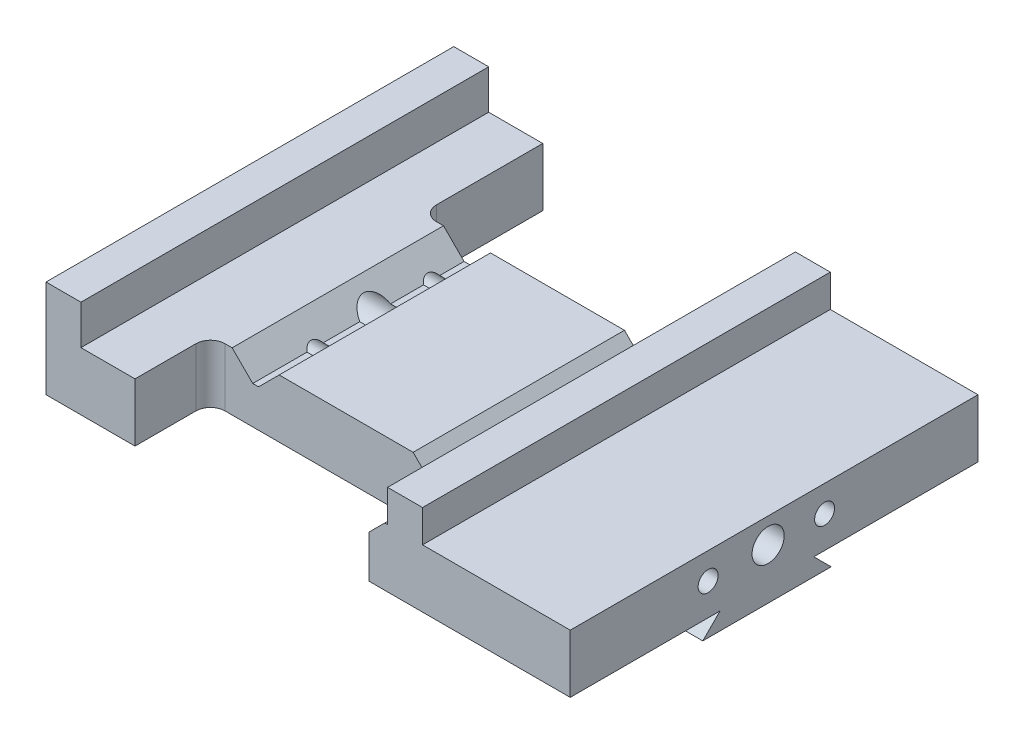
SolidWorks part; units mm, degrees
ref_plane "Front Plane" through (0, 0, 0) normal (0, 0, 1) x (1, 0, 0)
ref_plane "Top Plane" through (0, 0, 0) normal (0, 1, 0) x (1, 0, 0)
ref_plane "Right Plane" through (0, 0, 0) normal (1, 0, 0) x (0, 0, -1)
sketch "Sketch1" plane through (0, 0, 0) normal (0, 0, 1) x (1, 0, 0)
  line L0 (-151.9042, 0.4789) -> (-151.9042, 20.5906)
  line L1 (-151.9042, 20.5906) -> (-139.9042, 20.5906)
  line L2 (-139.9042, 20.5906) -> (-139.9042, 7.0711)
  line L3 (-139.9042, 7.0711) -> (-113.9042, 7.0711)
  line L4 (-113.9042, 7.0711) -> (-106.8331, 0)
  line L5 (-106.8331, 0) -> (-104.8331, 0)
  line L6 (-104.8331, 0) -> (-97.762, 7.0711)
  line L7 (-97.762, 7.0711) -> (-51.762, 7.0711)
  line L8 (-51.762, 7.0711) -> (-44.691, 0)
  line L9 (-44.691, 0) -> (-42.691, 0)
  line L10 (-42.691, 0) -> (-35.6199, 7.0711)
  line L11 (-35.6199, 7.0711) -> (-34.6199, 7.0711)
  line L12 (-34.6199, 7.0711) -> (-34.6199, 18.18)
  line L13 (-34.6199, 18.18) -> (-22.6199, 18.18)
  line L14 (-22.6199, 18.18) -> (-22.6199, 7.0711)
  line L15 (-22.6199, 7.0711) -> (28.0958, 7.0711)
  line L16 (28.0958, 7.0711) -> (28.0958, -12.9289)
  line L17 (28.0958, -12.9289) -> (-151.9042, -12.9289)
  line L18 (-151.9042, -12.9289) -> (-151.9042, 0.4789)
  dimension "D1" = 180
  dimension "D2" = 10
  dimension "D3" = 10
  dimension "D4" = 2
  dimension "D5" = 10
  dimension "D6" = 10
  dimension "D7" = 2
  dimension "D8" = 12
  dimension "D9" = 46
  dimension "D10" = 1
  dimension "D11" = 12
  dimension "D12" = 225
  dimension "D13" = 20
  dimension "D14" = 26
extrude "Boss-Extrude1" add sketch "Sketch1" along normal blind 140
sketch "Sketch2" plane through (28.0958, 0, 0) normal (1, 0, 0) x (0, 0, -1)
  line L0 (-88.5445, -12.9289) -> (-94.4984, -18.8828)
  line L1 (-140, -12.9289) -> (0, -12.9289) construction
  line L2 (-94.4984, -18.8828) -> (-50.4097, -18.8828)
  line L3 (-50.4097, -18.8828) -> (-56.3636, -12.9289)
  line L4 (-56.3636, -12.9289) -> (-88.5445, -12.9289)
  dimension "D1" = 45
  dimension "D2" = 45
extrude "Boss-Extrude2" add sketch "Sketch2" against normal blind 180
sketch "Sketch3" plane through (0, -12.9289, 0) normal (0, -1, 0) x (1, 0, 0)
  line L0 (-151.9042, 0) -> (28.0958, 0) construction
  line L1 (-121.3429, 0) -> (-41.0392, 0)
  line L2 (-121.3429, 0) -> (-121.3429, 36.5202)
  line L3 (-116.3429, 41.5202) -> (-46.0392, 41.5202)
  line L4 (-41.0392, 0) -> (-41.0392, 36.5202)
  line L5 (-151.9042, 140) -> (28.0958, 140) construction
  line L6 (-121.3429, 140) -> (-41.0392, 140)
  line L7 (-121.3429, 140) -> (-121.3429, 119.087)
  line L8 (-116.3429, 114.087) -> (-46.0392, 114.087)
  line L9 (-41.0392, 140) -> (-41.0392, 119.087)
  arc A0 (-46.0392, 41.5202) -> (-41.0392, 36.5202) centre (-46.0392, 36.5202) cw
  arc A1 (-121.3429, 36.5202) -> (-116.3429, 41.5202) centre (-116.3429, 36.5202) cw
  arc A2 (-46.0392, 114.087) -> (-41.0392, 119.087) centre (-46.0392, 119.087) ccw
  arc A3 (-121.3429, 119.087) -> (-116.3429, 114.087) centre (-116.3429, 119.087) ccw
  dimension "D1" = 5
extrude "Cut-Extrude1" cut sketch "Sketch3" against normal blind 100
sketch "Sketch4" plane through (28.0958, 0, 0) normal (1, 0, 0) x (0, 0, -1)
  circle A0 centre (-72.0525, -1.5555) radius 5.5191
extrude "Cut-Extrude2" cut sketch "Sketch4" against normal blind 1000
sketch "Sketch5" plane through (28.0958, 0, 0) normal (1, 0, 0) x (0, 0, -1)
  circle A0 centre (-92.6666, -2.0017) radius 3.4284
  circle A2 centre (-52.6666, -2.0017) radius 3.4284
  point P2 (-92.6666, -2.0017)
  dimension "D1" = 2
extrude "Cut-Extrude3" cut sketch "Sketch5" against normal blind 1000
